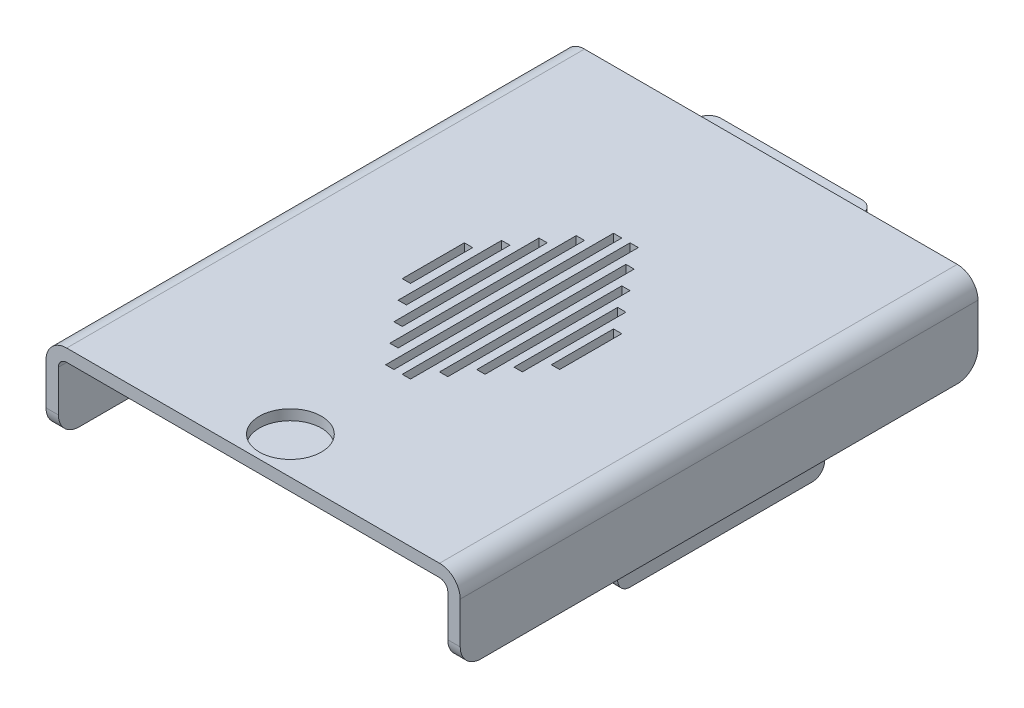
SolidWorks part; units mm, degrees
material "ABS"
ref_plane "Front Plane" through (0, 0, 0) normal (0, 0, 1) x (1, 0, 0)
ref_plane "Top Plane" through (0, 0, 0) normal (0, 1, 0) x (1, 0, 0)
ref_plane "Right Plane" through (0, 0, 0) normal (1, 0, 0) x (0, 0, -1)
sketch "Sketch1" plane through (0, 0, 0) normal (0, 0, 1) x (1, 0, 0)
  line L0 (-62.3906, 20.6479) -> (-62.3906, 26.5485) construction
  line L1 (-62.3906, 20.6479) -> (-62.3906, -14.3521) construction
  line L2 (-15.3906, 5.6479) -> (-15.3906, 20.6479)
  line L4 (-17.3906, 22.6479) -> (-107.3906, 22.6479)
  line L5 (-109.3906, 20.6479) -> (-109.3906, 5.6479)
  line L6 (-109.3906, 5.6479) -> (-112.3906, 5.6479)
  line L7 (-15.3906, 5.6479) -> (-12.3906, 5.6479)
  line L16 (-17.3906, 25.6479) -> (-107.3906, 25.6479)
  line L17 (-112.3906, 20.6479) -> (-112.3906, 5.6479)
  line L23 (-12.3906, 5.6479) -> (-12.3906, 20.6479)
  arc A0 (-107.3906, 25.6479) -> (-112.3906, 20.6479) centre (-107.3906, 20.6479) ccw
  arc A1 (-17.3906, 25.6479) -> (-12.3906, 20.6479) centre (-17.3906, 20.6479) cw
  arc A2 (-17.3906, 22.6479) -> (-15.3906, 20.6479) centre (-17.3906, 20.6479) cw
  arc A3 (-107.3906, 22.6479) -> (-109.3906, 20.6479) centre (-107.3906, 20.6479) ccw
  dimension "D4" = 20
  dimension "D5" = 100
  dimension "D1" = 5
  dimension "D2" = 3
  dimension "D3" = 20
extrude "Boss-Extrude1" add sketch "Sketch1" along normal blind 125
fillet "Fillet1" radius 5 4 edges at (-13.8906, 5.6479, 125) (-13.8906, 5.6479, 0) (-110.8906, 5.6479, 0) (-110.8906, 5.6479, 125)
sketch "Sketch2" plane through (0, 5.6479, 0) normal (0, -1, 0) x (1, 0, 0)
  line L1 (-107.3906, 35) -> (-110.3906, 35)
  line L2 (-107.3906, 35) -> (-107.3906, 85)
  line L3 (-107.3906, 85) -> (-110.3906, 85)
  line L4 (-110.3906, 35) -> (-110.3906, 85)
  line L6 (-82.3535, 85) -> (-109.3906, 85) construction
  line L7 (-109.3906, 120) -> (-109.3906, 5) construction
  line L9 (-12.3906, 35) -> (-12.3906, 85) construction
  line L10 (-15.3906, 85) -> (-12.3906, 85) construction
  line L11 (-15.3906, 35) -> (-15.3906, 85) construction
  line L12 (-15.3906, 35) -> (-12.3906, 35) construction
extrude "Boss-Extrude2" add sketch "Sketch2" against normal blind 18 and the other way blind 5
sketch "Sketch12" plane through (0, 5.6479, 0) normal (0, -1, 0) x (1, 0, 0)
  line L0 (-62.3906, 125) -> (-62.3906, 0) construction
  line L1 (-107.3906, 125) -> (-17.3906, 125) construction
  line L2 (-107.3906, 0) -> (-17.3906, 0) construction
  line L3 (-14.3906, 35) -> (-17.3906, 35)
  line L4 (-107.3906, 35) -> (-107.3906, 85)
  line L5 (-107.3906, 85) -> (-110.3906, 85)
  line L6 (-110.3906, 85) -> (-110.3906, 35)
  line L7 (-110.3906, 35) -> (-107.3906, 35)
  line L8 (-107.3906, 35) -> (-107.3906, 85) construction
  line L9 (-107.3906, 85) -> (-110.3906, 85) construction
  line L10 (-110.3906, 85) -> (-110.3906, 35) construction
  line L11 (-110.3906, 35) -> (-107.3906, 35) construction
  line L12 (-14.3906, 85) -> (-14.3906, 35)
  line L13 (-17.3906, 85) -> (-14.3906, 85)
  line L14 (-17.3906, 35) -> (-17.3906, 85)
  dimension "D1" = 0
extrude "Boss-Extrude5" add sketch "Sketch12" against normal blind 18 and the other way blind 5
sketch "Sketch3" plane through (0, 22.6479, 0) normal (0, -1, 0) x (1, 0, 0)
  line L0 (-62.3906, 0) -> (-62.3906, 120) construction
  line L1 (-42.3906, 10) -> (-82.3906, 10)
  line L2 (-42.3906, 10) -> (-42.3906, -5)
  line L3 (-42.3906, -5) -> (-82.3906, -5)
  line L4 (-82.3906, 10) -> (-82.3906, -5)
  line L5 (-62.3906, 125) -> (-62.3906, 127.9312) construction
  line L6 (-12.3906, 0) -> (-12.3906, 5) construction
  line L7 (-107.3906, 125) -> (-17.3906, 125) construction
  dimension "D1" = 20
  dimension "D2" = 40
  dimension "D3" = 15
  dimension "D4" = 50
extrude "Boss-Extrude3" add sketch "Sketch3" along normal blind 3
chamfer "Chamfer1" distance 4 angle 45 1 edges at (-62.3906, 22.6479, 10)
fillet "Fillet3" radius 4 2 edges at (-62.3906, 19.6479, 11) (-62.3906, 22.6479, 14)
fillet "Fillet4" radius 3 2 edges at (-82.3906, 21.1479, -5) (-42.3906, 21.1479, -5)
sketch "Sketch13" plane through (0, 25.6479, 0) normal (0, 1, 0) x (1, 0, 0)
  line L0 (-62.3906, 0) -> (-62.3906, -125) construction
  line L1 (-43.3906, -55) -> (-43.3906, -70)
  line L2 (-17.3906, -125) -> (-107.3906, -125) construction
  line L3 (-17.3906, 0) -> (-107.3906, 0) construction
  line L4 (-63.3906, -35) -> (-65.3906, -35)
  line L5 (-63.3906, -35) -> (-63.3906, -90)
  line L6 (-63.3906, -90) -> (-65.3906, -90)
  line L7 (-65.3906, -35) -> (-65.3906, -90)
  line L8 (-62.3906, -62.5) -> (-51.3906, -62.5) construction
  line L10 (-67.3906, -40) -> (-69.3906, -40)
  line L11 (-67.3906, -40) -> (-67.3906, -85)
  line L12 (-67.3906, -85) -> (-69.3906, -85)
  line L13 (-69.3906, -40) -> (-69.3906, -85)
  line L14 (-71.3906, -45) -> (-73.3906, -45)
  line L15 (-71.3906, -45) -> (-71.3906, -80)
  line L16 (-71.3906, -80) -> (-73.3906, -80)
  line L17 (-73.3906, -45) -> (-73.3906, -80)
  line L21 (-55.3906, -40) -> (-55.3906, -85)
  line L22 (-57.3906, -85) -> (-55.3906, -85)
  line L23 (-57.3906, -40) -> (-57.3906, -85)
  line L24 (-57.3906, -40) -> (-55.3906, -40)
  line L25 (-59.3906, -35) -> (-59.3906, -90)
  line L26 (-61.3906, -90) -> (-59.3906, -90)
  line L27 (-61.3906, -35) -> (-61.3906, -90)
  line L28 (-61.3906, -35) -> (-59.3906, -35)
  line L29 (-75.3906, -50) -> (-77.3906, -50)
  line L30 (-75.3906, -50) -> (-75.3906, -75)
  line L31 (-75.3906, -75) -> (-77.3906, -75)
  line L32 (-77.3906, -50) -> (-77.3906, -75)
  line L33 (-79.3906, -55) -> (-81.3906, -55)
  line L34 (-79.3906, -55) -> (-79.3906, -70)
  line L35 (-79.3906, -70) -> (-81.3906, -70)
  line L36 (-81.3906, -55) -> (-81.3906, -70)
  line L37 (-45.3906, -70) -> (-43.3906, -70)
  line L38 (-45.3906, -55) -> (-45.3906, -70)
  line L39 (-45.3906, -55) -> (-43.3906, -55)
  line L40 (-47.3906, -50) -> (-47.3906, -75)
  line L41 (-49.3906, -75) -> (-47.3906, -75)
  line L42 (-49.3906, -50) -> (-49.3906, -75)
  line L43 (-49.3906, -50) -> (-47.3906, -50)
  line L44 (-51.3906, -45) -> (-51.3906, -80)
  line L45 (-53.3906, -80) -> (-51.3906, -80)
  line L46 (-53.3906, -45) -> (-53.3906, -80)
  line L47 (-53.3906, -45) -> (-51.3906, -45)
extrude "Cut-Extrude1" cut sketch "Sketch13" against normal up to surface (3 mm away) up to face at (-62.3906, 22.6479, 43.4428)
fillet "Fillet5" radius 3 4 edges at (-108.8906, 0.6479, 85) (-108.8906, 0.6479, 35) (-15.8906, 0.6479, 35) (-15.8906, 0.6479, 85)
fillet "Fillet6" radius 3 2 edges at (-17.3906, 22.6479, 60) (-107.3906, 22.6479, 60)
sketch "Sketch14" plane through (0, 25.6479, 0) normal (0, 1, 0) x (1, 0, 0)
  line L2 (-17.3906, -125) -> (-107.3906, -125) construction
  line L3 (-62.3906, -125) -> (-62.3906, -116) construction
  line L4 (-12.3906, -116) -> (-62.3906, -116) construction
  line L5 (-12.3906, -125) -> (-12.3906, 0) construction
  circle A1 centre (-62.3906, -116) radius 7.5
extrude "Cut-Extrude2" cut sketch "Sketch14" against normal blind 2.5
